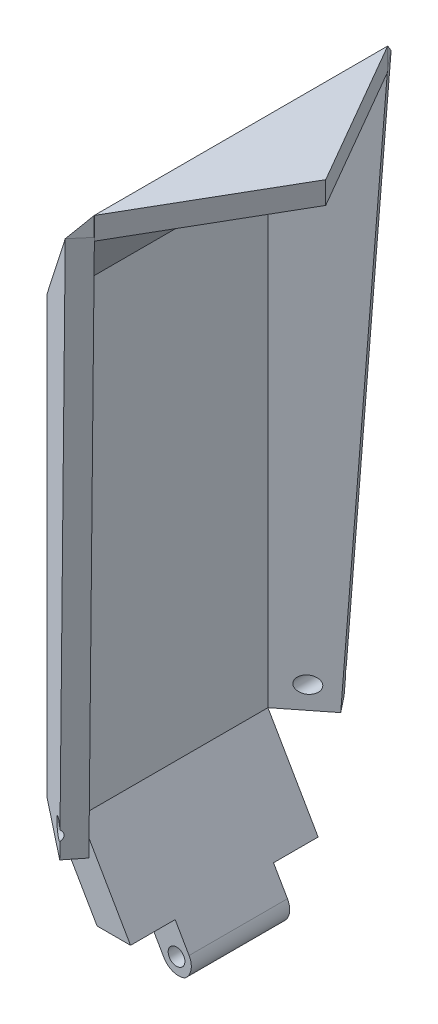
SolidWorks part; units mm, degrees
material "Custom Plastic"
ref_plane "Front Plane" through (0, 0, 0) normal (0, 0, 1) x (1, 0, 0)
ref_plane "Top Plane" through (0, 0, 0) normal (0, 1, 0) x (1, 0, 0)
ref_plane "Right Plane" through (0, 0, 0) normal (1, 0, 0) x (0, 0, -1)
sketch "Sketch1" plane through (0, 0, 0) normal (0, 1, 0) x (1, 0, 0)
  line L4 (0, 0) -> (0, 16.82)
  line L5 (0, 16.82) -> (7.8551, 23.0085)
  line L6 (7.8551, 23.0085) -> (9.004, 21.5502)
  line L7 (9.004, 21.5502) -> (3, 16.82)
  line L8 (3, 16.82) -> (3, 0)
  line L9 (3, 0) -> (8.9971, -4.739)
  line L10 (8.9971, -4.739) -> (7.846, -6.2)
  line L11 (7.846, -6.2) -> (0, 0)
  dimension "D1" = 16.82
  dimension "D2" = 10
  dimension "D3" = 10
  dimension "D4" = 3
  dimension "D5" = 1.86
  dimension "D6" = 1.8566
extrude "Boss-Extrude1" add sketch "Sketch1" along normal blind 50
sketch "Sketch8" plane through (0, 0, 0) normal (0, 0, 1) x (1, 0, 0)
  line L0 (0, 0) -> (5.9985, -10.3896) construction
  line L2 (0, 50) -> (0, 0) construction
  line L3 (3, 0) -> (7, 0) construction
  dimension "D1" = 150
  dimension "3.5" = 4
sketch "Sketch2" plane through (0, 0, 0) normal (-0.62, 0, 0.7846) x (0.7846, 0, 0.62)
  line L0 (11.46, 50) -> (0, 37)
  line L1 (0, 50) -> (0, 0) construction
  line L2 (0, 37) -> (0, 50)
  line L3 (0, 50) -> (11.46, 50)
  dimension "D1" = 13
  dimension "D2" = 11.46
extrude "Cut-Extrude1" cut sketch "Sketch2" along direction (0, 0, 1) on the side against the normal blind 30
sketch "Sketch5" plane through (-17.3103, 11.9728, 0) normal (-0.8224, 0.5688, 0) x (0, 0, 1)
  line L0 (0, 30.4304) -> (6.2, 44.2232)
  line L1 (6.2, 44.2232) -> (4.746, 46.2369)
  line L5 (-21.566, 46.2369) -> (-23.0085, 44.2391)
  line L6 (-23.0085, 44.2391) -> (-16.82, 30.4304)
  line L7 (-16.82, 30.4304) -> (0, 30.4304)
  line L8 (-21.566, 46.2369) -> (4.746, 46.2369)
extrude "Boss-Extrude2" add sketch "Sketch5" along direction (0, -1, 0) on the side of the normal blind 2 contours L8 L1 L0 L7 L6 L5
sketch "Sketch6" plane through (0, 0, 0) normal (-0.62, 0, 0.7846) x (0.7846, 0, 0.62)
  line L0 (10, 50.3438) -> (7, 0)
  line L2 (7, 0) -> (10, 0)
  line L3 (10, 0) -> (10, 50.3438)
  dimension "D1" = 3
extrude "Cut-Extrude2" cut sketch "Sketch6" against normal blind 2
sketch "Sketch7" plane through (-8.1764, 0, -10.3783) normal (-0.6189, 0, -0.7855) x (-0.7855, 0, 0.6189)
  line L0 (-20.4091, 50.3569) -> (-20.4091, 0)
  line L1 (-20.4091, 0) -> (-17.4091, 0)
  line L3 (-17.4091, 0) -> (-20.4091, 50.3569)
  dimension "D1" = 3
extrude "Cut-Extrude3" cut sketch "Sketch7" against normal blind 2
sketch "Sketch9" plane through (0, 0, 0) normal (0, -1, 0) x (1, 0, 0)
  line L0 (0, 0) -> (3, 0)
  line L1 (3, 0) -> (3, -16.82)
  line L2 (3, -16.82) -> (0, -16.82)
  line L3 (0, -16.82) -> (0, 0)
extrude "Boss-Extrude3" add sketch "Sketch9" along direction (0.5, -0.866, 0) on the side of the normal blind 13
sketch "Sketch10" plane through (0, 0, 0) normal (-0.866, -0.5, 0) x (0, 0, 1)
  line L0 (-16.82, -9) -> (-12.82, -9)
  line L1 (-16.82, -13) -> (-16.82, 0) construction
  line L2 (-12.82, -9) -> (-12.82, -13)
  line L3 (0, -13) -> (-16.82, -13) construction
  line L4 (-12.82, -13) -> (-16.82, -13)
  line L5 (-16.82, -13) -> (-16.82, -9)
  line L6 (0, -9) -> (-4, -9)
  line L7 (0, -13) -> (0, 0) construction
  line L8 (-4, -9) -> (-4, -13)
  line L9 (-4, -13) -> (0, -13)
  line L10 (0, -13) -> (0, -9)
  dimension "D1" = 4
  dimension "D2" = 4
  dimension "D3" = 4
extrude "Cut-Extrude4" cut sketch "Sketch10" along direction (1, 0, 0) on the side against the normal blind 15
sketch "Sketch11" plane through (0, 0, -12.82) normal (0, 0, -1) x (-1, 0, 0)
  line L4 (-9.5, -11.2583) -> (-7.25, -12.5574)
  line L5 (-7.25, -12.5574) -> (-6.5, -11.2583)
  line L6 (-6.5, -11.2583) -> (-9.5, -11.2583)
  line L8 (-9.5, -11.2583) -> (-7.5, -7.7942) construction
  line L9 (-6.5, -11.2583) -> (-4.5, -7.7942) construction
extrude "Boss-Extrude4" add sketch "Sketch11" against normal up to surface (8.82 mm away) contours L4 L5 L6 up to face at (7, -9.5263, -4)
fillet "Fillet1" radius 1.5 2 edges at (9.5, -11.2583, -8.41) (7.25, -12.5574, -8.41)
sketch "Sketch12" plane through (0, 0, -4) normal (0, 0, 1) x (1, 0, 0)
  line L0 (8.75, -9.9593) -> (6.5, -11.2583) construction
  circle A0 centre (7.625, -10.6088) radius 0.75
  point P8 (7.625, -10.6088)
  dimension "D1" = 1.5
extrude "Cut-Extrude5" cut sketch "Sketch12" against normal through all
sketch "Sketch15" plane through (0, 0, 0) normal (0, 0, 1) x (1, 0, 0)
  line L0 (3, 0) -> (7, 0) construction
  circle A0 centre (5, 2) radius 0.75
  point P5 (5, 0)
  dimension "D1" = 1.5
  dimension "D2" = 2
  dimension "D3" = 2
extrude "Cut-Extrude7" cut sketch "Sketch15" against normal through all and the other way through all
sketch "Sketch17" plane through (8.9915, 0, 0) normal (1, 0, 0) x (0, 0, -1)
  line L0 (-4.746, 52) -> (-4.7173, 50)
  line L1 (-4.7173, 50) -> (21.5317, 50)
  line L2 (21.5317, 50) -> (21.566, 52)
  line L3 (21.566, 52) -> (-4.746, 52)
extrude "Boss-Extrude5" add sketch "Sketch17" along normal blind 7.6
sketch "Sketch18" plane through (0, 52, 0) normal (0, 1, 0) x (1, 0, 0)
  line L0 (8.9915, 21.566) -> (16.5915, 8.41)
  line L1 (16.5915, 21.566) -> (16.5915, -4.746) construction
  line L4 (8.9915, 21.566) -> (16.5915, 21.566)
  line L5 (16.5915, 21.566) -> (16.5915, 8.41)
extrude "Cut-Extrude8" cut sketch "Sketch18" against normal blind 3
sketch "Sketch19" plane through (0, 52, 0) normal (0, 1, 0) x (1, 0, 0)
  line L0 (16.5915, 8.41) -> (8.9915, -4.746)
  line L1 (8.9915, -4.746) -> (16.5915, -4.746)
  line L2 (16.5915, -4.746) -> (16.5915, 8.41)
extrude "Cut-Extrude9" cut sketch "Sketch19" against normal blind 3
scale "Scale1" scale about centroid uniform scaling yes scale factor 1.3
equation "\"8.5.000000mm\"=9"
